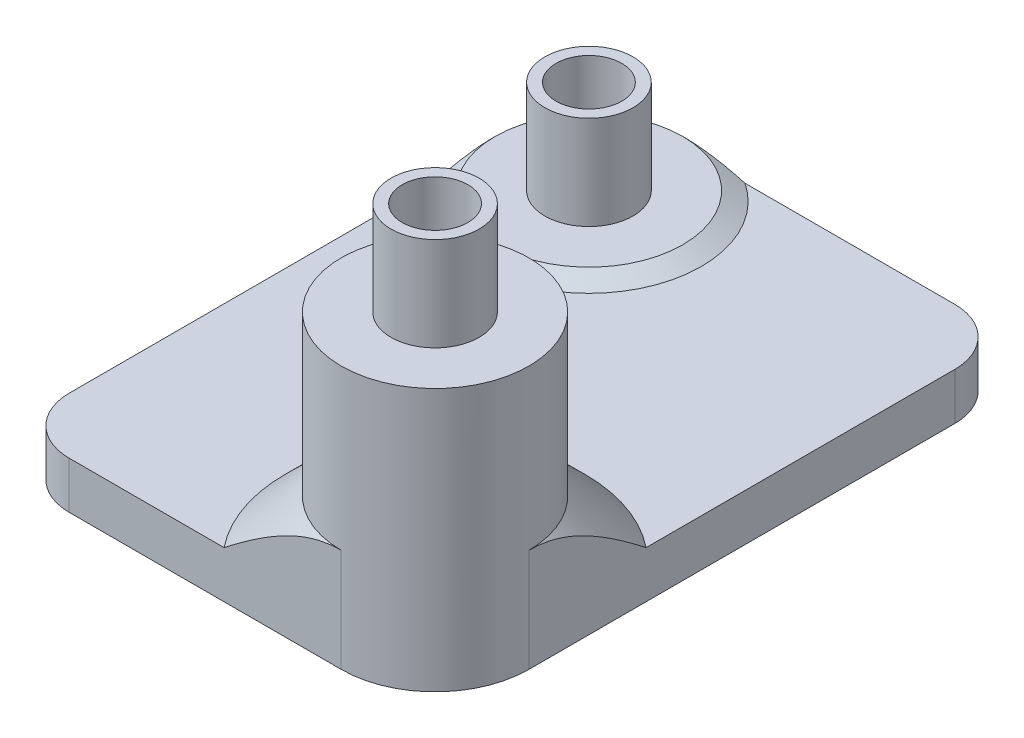
SolidWorks part; units mm, degrees
ref_plane "Front Plane" through (0, 0, 0) normal (0, 0, 1) x (1, 0, 0)
ref_plane "Top Plane" through (0, 0, 0) normal (0, 1, 0) x (1, 0, 0)
ref_plane "Right Plane" through (0, 0, 0) normal (1, 0, 0) x (0, 0, -1)
sketch "Sketch1" plane through (0, 0, 0) normal (0, 1, 0) x (1, 0, 0)
  line L0 (0, 0) -> (-12.5, 20.7) construction
  line L1 (-17.5, 10.35) -> (5, 10.35) construction
  line L2 (-12.5, 25.7) -> (5, 25.7)
  line L3 (-17.5, 20.7) -> (-17.5, -5)
  line L4 (-17.5, -5) -> (0, -5)
  line L5 (5, 25.7) -> (5, 0)
  line L6 (5, 0) -> (5, -5)
  line L7 (5, -5) -> (0, -5)
  line L8 (-17.5, 20.7) -> (-17.5, 25.7)
  line L9 (-17.5, 25.7) -> (-2.1039, 25.7)
  circle A0 centre (0, 0) radius 1.75
  circle A1 centre (-12.5, 20.7) radius 1.75
  circle A2 centre (-12.5, 20.7) radius 5
  circle A3 centre (0, 0) radius 5
  arc A4 (-12.5, 25.7) -> (-17.5, 20.7) centre (-12.5, 20.7) ccw construction
  arc A5 (0, -5) -> (5, 0) centre (0, 0) ccw construction
  arc A8 (-17.5, 20.7) -> (-9.9154, 16.4199) centre (-12.5, 20.7) ccw construction
  arc A9 (-9.9154, 16.4199) -> (-12.5, 25.7) centre (-12.5, 20.7) ccw construction
  arc A10 (5, 0) -> (-2.5846, 4.2801) centre (0, 0) ccw construction
  arc A11 (-2.5846, 4.2801) -> (0, -5) centre (0, 0) ccw construction
  point P13 (-6.25, 10.35)
  dimension "6" = 3.5
  dimension "D4" = 10
  dimension "D5" = 10
  dimension "D1" = 12.5
  dimension "D2" = 20.7
extrude "Boss-Extrude1" add sketch "Sketch1" against normal blind 2.5 contours L3 L4 A5 L5 L2 A4 A2 A3 | A2 A1 | A3 A0 region at (-6.25, 0, -10.35) region at (-9.0645, 0, -24.1355) region at (3.4355, 0, 3.4355)
extrude "Boss-Extrude2" add sketch "Sketch1<3>" along normal blind 0.5 contours A2 A1 region at (-9.0645, 0, -24.1355)
sketch "Sketch1<3>" plane through (0, 0, 0) normal (0, 1, 0) x (1, 0, 0) same geometry as "Sketch1"
extrude "Boss-Extrude3" add sketch "Sketch1<4>" along normal blind 11.5 contours A3 A0 region at (3.4355, 0, 3.4355)
sketch "Sketch1<4>" plane through (0, 0, 0) normal (0, 1, 0) x (1, 0, 0) same geometry as "Sketch1"
fillet "Fillet4" radius 3 2 edges at (5, -1.25, -25.7) (-17.5, -1.25, 5)
chamfer "Chamfer1" distance 1 distance2 0.5 1 edges at (-8.9645, 0, -17.1645) first distance on face at (-6.25, 0, -10.35)
chamfer "Chamfer2" distance 3 distance2 3 1 edges at (-3.5355, 0, -3.5355)
sketch "Sketch2" plane through (0, 0.5, 0) normal (0, 1, 0) x (1, 0, 0)
  circle A0 centre (-12.5, 20.7) radius 2.35
  circle A1 centre (-12.5, 20.7) radius 1.75 construction
  circle A2 centre (-12.5, 20.7) radius 1.75
  dimension "D1" = 4.7
extrude "Boss-Extrude4" add sketch "Sketch2" along normal blind 5
sketch "Sketch3" plane through (0, 11.5, 0) normal (0, 1, 0) x (1, 0, 0)
  circle A0 centre (0, 0) radius 2.35
  circle A1 centre (-12.5, 20.7) radius 2.35 construction
  circle A2 centre (0, 0) radius 1.75 construction
  circle A3 centre (0, 0) radius 1.75
extrude "Boss-Extrude5" add sketch "Sketch3" along normal blind 5
